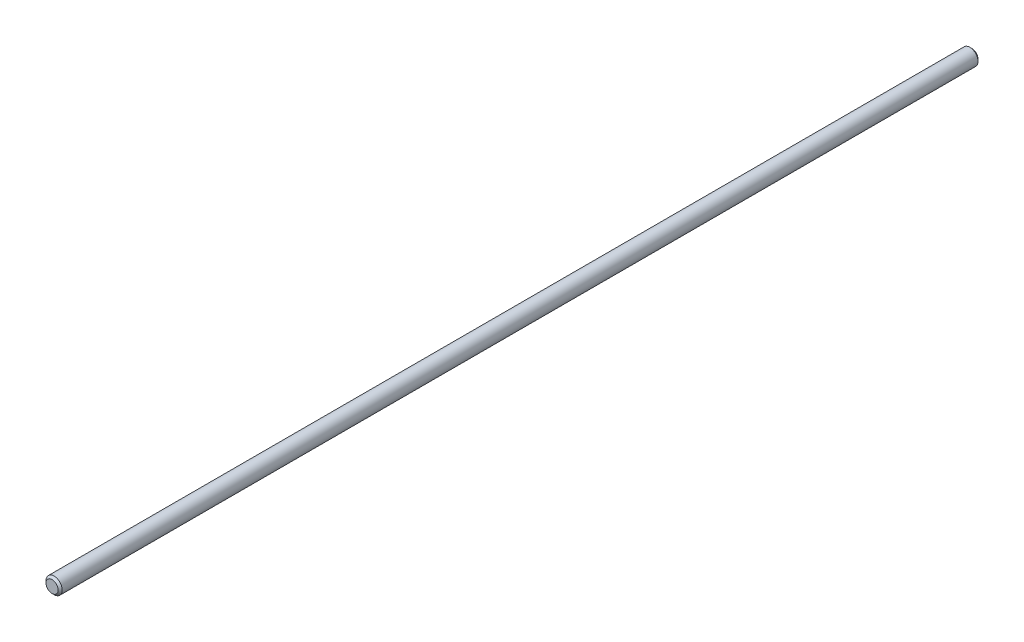
SolidWorks part; units mm, degrees
ref_plane "Piano frontale" through (0, 0, 0) normal (0, 0, 1) x (1, 0, 0)
ref_plane "Piano superiore" through (0, 0, 0) normal (0, 1, 0) x (1, 0, 0)
ref_plane "Piano destro" through (0, 0, 0) normal (1, 0, 0) x (0, 0, -1)
sketch "Schizzo1" plane through (0, 0, 0) normal (0, 0, 1) x (1, 0, 0)
  circle A0 centre (0, 0) radius 4
  dimension "D1" = 8
extrude "Estrusione-Estrusione1" add sketch "Schizzo1" along normal blind 455
chamfer "Smusso1" distance 1 angle 45 2 edges at (4, 0, 0) (4, 0, 455)
sketch "Schizzo2" plane through (0, 0, 0) normal (0, 1, 0) x (1, 0, 0)
  line L0 (4, -1) -> (4, -454) construction
